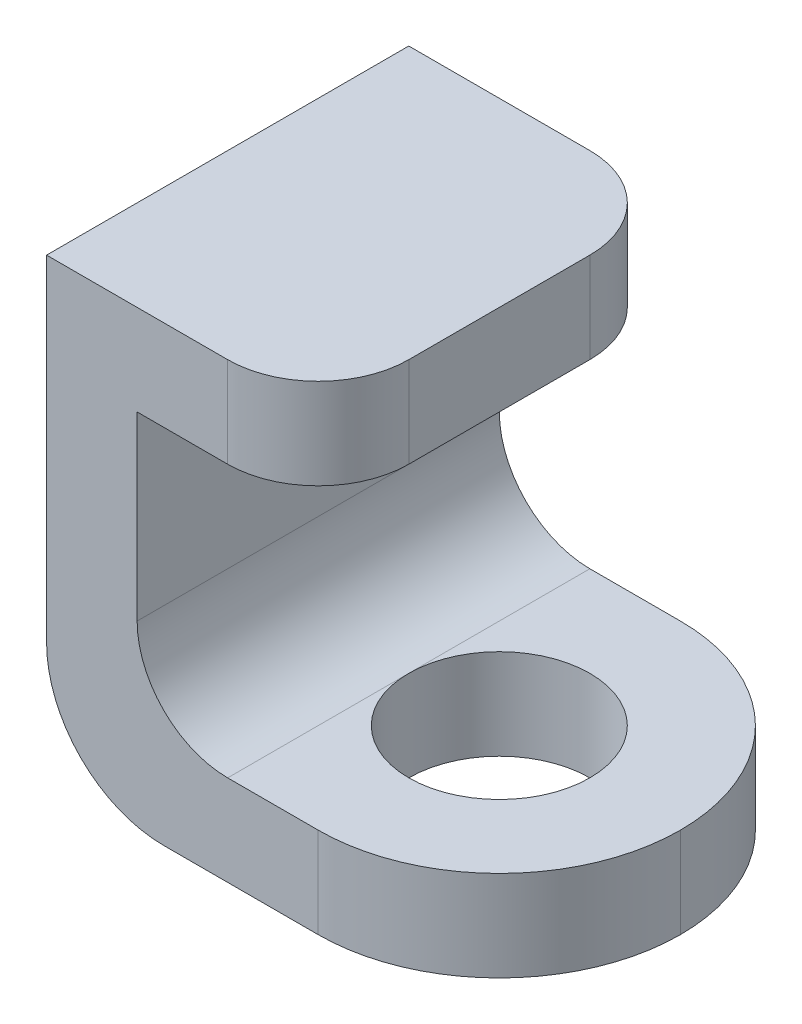
SolidWorks part; units mm, degrees
ref_plane "前基準面" through (0, 0, 0) normal (0, 0, 1) x (1, 0, 0)
ref_plane "上基準面" through (0, 0, 0) normal (0, 1, 0) x (1, 0, 0)
ref_plane "右基準面" through (0, 0, 0) normal (1, 0, 0) x (0, 0, -1)
sketch "草圖1" plane through (0, 0, 0) normal (0, 1, 0) x (1, 0, 0)
  line L1 (-25, -20) -> (25, -20)
  line L2 (-25, -20) -> (-25, 20)
  line L3 (-25, 20) -> (25, 20)
  line L4 (25, -20) -> (25, 20)
  line L5 (-25, -20) -> (25, 20) construction
  line L6 (-25, 20) -> (25, -20) construction
  point P0 (0, 0)
  dimension "D1" = 50
  dimension "D2" = 40
extrude "填料-伸長1" add sketch "草圖1" along normal blind 50
sketch "草圖2" plane through (0, 0, 20) normal (0, 0, 1) x (1, 0, 0)
  line L0 (5, 50) -> (5, 40)
  line L1 (-25, 50) -> (25, 50) construction
  line L2 (5, 40) -> (-15, 40)
  line L3 (-15, 40) -> (-15, 20)
  line L4 (-5, 10) -> (25, 10)
  line L5 (25, 50) -> (25, 0) construction
  line L6 (25, 10) -> (25, 0)
  line L7 (25, 0) -> (-12.0711, 0)
  line L8 (-25, 0) -> (25, 0) construction
  line L9 (-25, 50) -> (-25, 0) construction
  line L10 (-25, 12.9289) -> (-25, 50)
  line L11 (-25, 50) -> (5, 50)
  line L12 (5, 50) -> (25, 50)
  line L13 (25, 50) -> (25, 10)
  line L14 (-25, 12.9289) -> (-25, 0)
  line L15 (-25, 0) -> (-12.0711, 0)
  arc A0 (-15, 20) -> (-5, 10) centre (-5, 20) ccw
  arc A1 (-12.0711, 0) -> (-25, 12.9289) centre (-12.0711, 12.9289) cw
  line M6 (-25, 0) -> (25, 0)
  line M7 (25, 0) -> (25, 50)
  line M8 (25, 50) -> (-25, 50)
  line M9 (-25, 50) -> (-25, 0)
  dimension "D5" = 10
  dimension "D1" = 10
  dimension "D2" = 20
  dimension "D3" = 10
  dimension "D4" = 10
  dimension "D6" = 30
extrude "除料-伸長1" cut sketch "草圖2" against normal through all contours L3 A0 L4 L0 L2 M7 M8 | A1 M6 M9 region at (6.7274, 28.1004, 20) region at (-22.1121, 2.8879, 20)
fillet "圓角1" radius 10 2 edges at (5, 45, -20) (5, 45, 20)
fillet "圓角2" radius 20 2 edges at (25, 5, -20) (25, 5, 20)
sketch "草圖4" plane through (0, 10, 0) normal (0, 1, 0) x (1, 0, 0)
  circle A0 centre (5, 0) radius 10
  dimension "D1" = 20
extrude "除料-伸長2" cut sketch "草圖4" against normal blind 50
